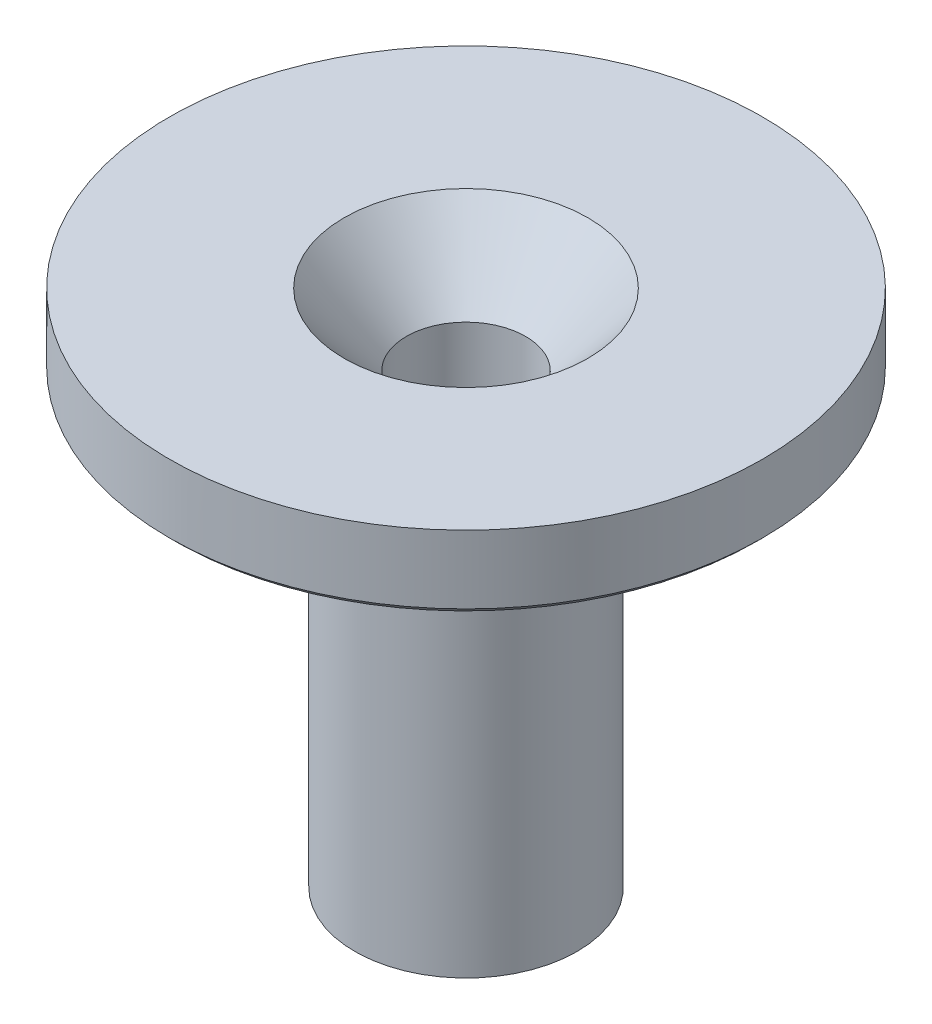
SolidWorks part; units mm, degrees
ref_plane "Front Plane" through (0, 0, 0) normal (0, 0, 1) x (1, 0, 0)
ref_plane "Top Plane" through (0, 0, 0) normal (0, 1, 0) x (1, 0, 0)
ref_plane "Right Plane" through (0, 0, 0) normal (1, 0, 0) x (0, 0, -1)
sketch "Sketch2" plane through (0, 0, 0) normal (0, 0, 1) x (1, 0, 0)
  line L0 (0, 10.1405) -> (-12.7, 10.1405)
  line L1 (0, -55) -> (0, 55) construction
  line L2 (-12.7, 10.1405) -> (-12.7, 6.9655)
  line L3 (-12.7, 6.9655) -> (-4.7625, 6.9655)
  line L4 (-4.7625, 6.9655) -> (-4.7625, -12.0845)
  line L5 (-4.7625, -12.0845) -> (0, -12.0845)
  line L6 (0, -12.0845) -> (0, 10.1405) construction
  line L7 (0, 10.1405) -> (0, -12.0845)
  point P8 (-2.3812, -12.0845)
  point P9 (-7.4317, -19.2608)
  dimension "D1" = 19.05
  dimension "D2" = 12.7
  dimension "D3" = 4.7625
  dimension "D4" = 3.175
revolve "Revolve1" add sketch "Sketch2" angle 360 about L6
hole_wizard "CSK for #10 Flat Head Socket Cap Screw1" positions "Sketch3" profile "Sketch4" countersink size "#10" standard "ANSI Inch" end condition through all
sketch "Sketch3" plane through (0, 10.1405, 0) normal (0, 1, 0) x (1, 0, 0)
  point P0 (0, 0)
sketch "Sketch4" plane through (0, 10.1405, 0) normal (1, 0, 0) x (0, 0, 1)
  line L0 (0, 0) -> (0, 22.225)
  line L1 (0, 22.225) -> (2.5527, 22.225)
  line L2 (2.5527, 22.225) -> (2.5527, 3.068)
  line L3 (2.5527, 3.068) -> (5.2197, 0)
  line L5 (5.2197, 0) -> (0, 0)
  line L6 (-2.5527, 3.068) -> (-5.2197, 0) construction
  line L11 (0, -6.35) -> (0, 107.95) construction
  dimension "Thru Hole Dia." = 5.1054
  dimension "Thru Hole Depth" = 22.225
  dimension "Near C'Sink Dia." = 10.4394
  dimension "Near C'Sink Angle" = 82
chamfer "Chamfer1" distance 0.254 angle 45 1 edges at (12.7, 6.9655, 0)
